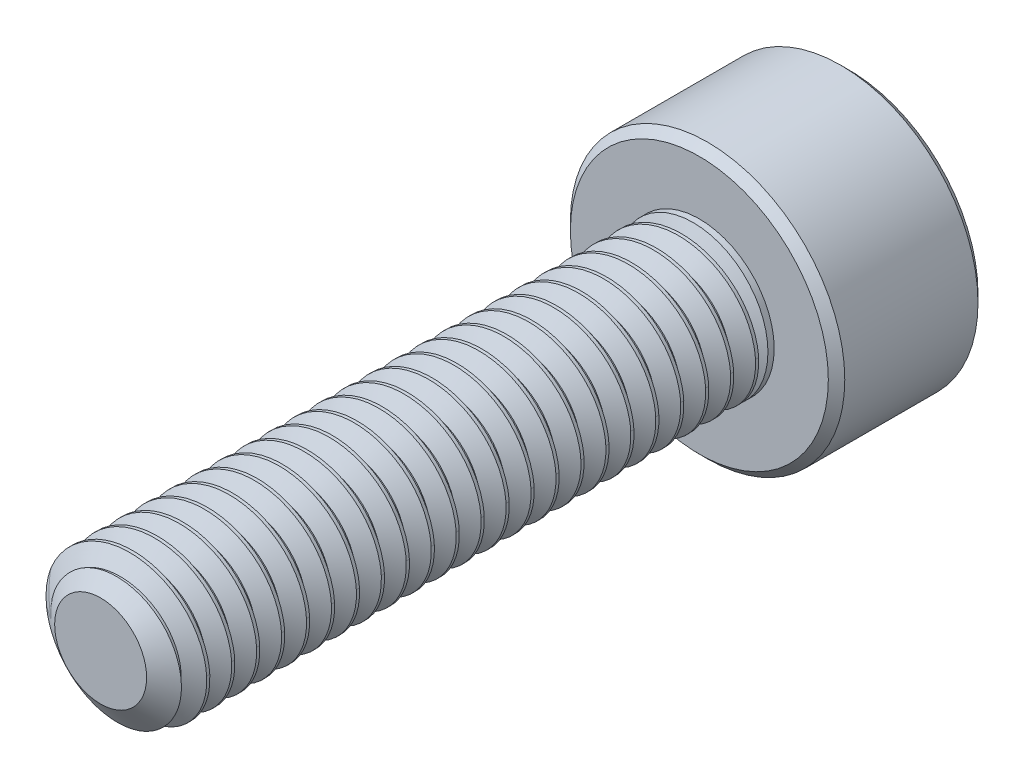
SolidWorks part; units mm, degrees
ref_plane "Front Plane" through (0, 0, 0) normal (0, 0, 1) x (1, 0, 0)
ref_plane "Top Plane" through (0, 0, 0) normal (0, 1, 0) x (1, 0, 0)
ref_plane "Right Plane" through (0, 0, 0) normal (1, 0, 0) x (0, 0, -1)
sketch "Sketch1" plane through (0, 0, 0) normal (0, 0, 1) x (1, 0, 0)
  circle A0 centre (0, 0) radius 1.5
  dimension "OD" = 3
extrude "Extrude1" add sketch "Sketch1" against normal blind 12
sketch "Sketch2" plane through (0, 0, 0) normal (0, 0, 1) x (1, 0, 0)
  circle A0 centre (0, 0) radius 1.5 construction
  circle A1 centre (0, 0) radius 1.5
curve "Helix/Spiral1" pitch 0.5 height 12.5 radius 1.5 centre (0, 0, 0) axis (0, 0, -1) start towards (0, 1, 0) parameters "pitch"=0.5
sketch "Sketch3" plane through (0, 0, 0) normal (1, 0, 0) x (0, 0, -1)
  line L0 (-0.4375, 1.5) -> (-0.25, 1.1752)
  line L1 (-0.25, 1.1752) -> (-0.1875, 1.1752)
  line L2 (-0.1875, 1.1752) -> (0, 1.5)
  line L3 (-0.4375, 1.5) -> (0, 1.5)
  line L4 (-0.2187, 1.5) -> (-0.2187, 1.1752) construction
  line L5 (-0.3437, 1.3376) -> (-0.0937, 1.3376) construction
  line L6 (0, 1.5) -> (0, -1.5) construction
  line L7 (0, -1.5) -> (12, -1.5) construction
  point P11 (2.25, -1.5)
  dimension "D1" = 0.0625
  dimension "D2" = 0.25
  dimension "D3" = 60
  dimension "D4" = 2.25
sweep "Cut-Sweep1" cut profiles "Sketch3" path "Helix/Spiral1"
sketch "Sketch4" plane through (0, 0, 0) normal (1, 0, 0) x (0, 0, -1)
  line L0 (0.4053, 1.5) -> (0, 0.9212)
  line L1 (0, 0.9212) -> (0, 1.5)
  line L2 (0.4053, 1.5) -> (0, 1.5)
  line L3 (-0.4375, 1.5) -> (0, 1.5) construction
  line L4 (0, 0) -> (7.0209, 0) construction
  dimension "D1" = 55
  dimension "D2" = 0.254
revolve "Cut-Revolve1" cut sketch "Sketch4" angle 360 about L4
sketch "Sketch5" plane through (0, 0, 0) normal (1, 0, 0) x (0, 0, -1)
  line L0 (12, -1.1822) -> (12, 1.0703) construction
  line L1 (12, 1.5) -> (0.1203, 1.5)
  line L2 (12, 1.5) -> (12, 0)
  line L3 (12, 0) -> (0.0001, 0)
  line L4 (0.0001, 1.1698) -> (0.0001, 0)
  line L5 (0.1203, 1.5) -> (0.0001, 1.1698)
  line L6 (0, 0) -> (9.9695, 0) construction
  point P3 (0.0001, 1.5)
  point P10 (0.0001, 1.5)
  dimension "D1" = 0.3302
  dimension "Thread min" = 0.0001
  dimension "D3" = 20
revolve "partially thread" [suppressed] add sketch "Sketch5" angle 360 about L6
sketch "Sketch6" plane through (0, 0, -12) normal (0, 0, -1) x (-1, 0, 0)
  circle A0 centre (0, 0) radius 2.75
  dimension "head dia" = 5.5
extrude "Extrude2" add sketch "Sketch6" along normal blind 3
sketch "Sketch7" plane through (0, 0, -15) normal (0, 0, -1) x (-1, 0, 0)
  line L1 (0, 1.4434) -> (-1.25, 0.7217)
  line L2 (-1.25, 0.7217) -> (-1.25, -0.7217)
  line L3 (-1.25, -0.7217) -> (0, -1.4434)
  line L4 (0, -1.4434) -> (1.25, -0.7217)
  line L5 (1.25, -0.7217) -> (1.25, 0.7217)
  line L6 (1.25, 0.7217) -> (0, 1.4434)
  circle A0 centre (0, 0) radius 1.25 construction
  dimension "hex dia" = 2.5
extrude "Cut-Extrude1" cut sketch "Sketch7" against normal blind 1.875
sketch "Sketch8" plane through (0, 0, -15) normal (0, 0, -1) x (-1, 0, 0)
  circle A0 centre (0, 0) radius 1.4434
extrude "Cut-Extrude2" cut sketch "Sketch8" against normal through all draft 45
chamfer "Chamfer1" distance 0.165 angle 45 2 edges at (-2.75, 0, -15) (-2.75, 0, -12)
sketch "Sketch9" plane through (0, 0, 0) normal (1, 0, 0) x (0, 0, -1)
  line L0 (0, 1.5) -> (0, -1.5) construction
  line L1 (2.75, 1.5) -> (2.75, -1.5) construction
  dimension "D1" = 2.75
sketch "Sketch10" plane through (0, 0, 0) normal (1, 0, 0) x (0, 0, -1)
  line L0 (12, 1.5) -> (12, 0)
  line L1 (12, 1.5) -> (11.875, 1.5)
  line L2 (11.875, 1.5) -> (11.2537, 0)
  line L3 (12, 0) -> (11.2537, 0)
  line L4 (12, 2.585) -> (12, -2.585) construction
  dimension "D1" = 22.5
  dimension "D2" = 0.125
revolve "Revolve1" add sketch "Sketch10" angle 360 about L3
equation "\"D3@Helix/Spiral1\" = \"screw length@Extrude1\"+\"pitch@Helix/Spiral1\""
equation "\"D1@Sketch3\" = \"pitch@Helix/Spiral1\"*.125"
equation "\"D2@Sketch3\" = \"pitch@Helix/Spiral1\"*.5"
equation "\"D1@Cut-Extrude1\" = \"hex dia@Sketch7\"*.75"
equation "\"D1@Chamfer1\" = \"head dia@Sketch6\"*.03"
equation "\"D1@Sketch9\" = \"pitch@Helix/Spiral1\"*5.5"
equation "\"D2@Sketch10\" = \"pitch@Helix/Spiral1\"*.25"
equation "\"D4@Sketch3\" = \"pitch@Helix/Spiral1\"*4.50"
